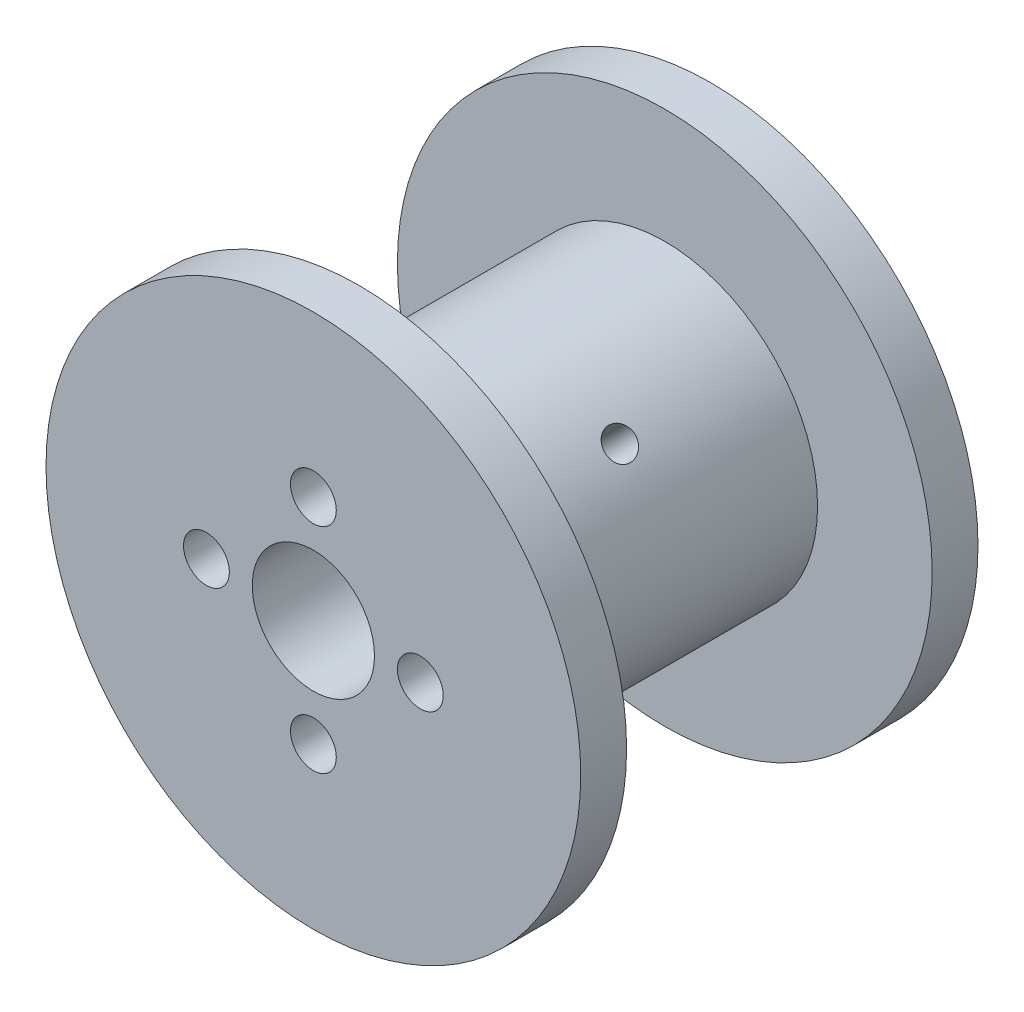
SolidWorks part; units mm, degrees
ref_plane "前视基准面" through (0, 0, 0) normal (0, 0, 1) x (1, 0, 0)
ref_plane "上视基准面" through (0, 0, 0) normal (0, 1, 0) x (1, 0, 0)
ref_plane "右视基准面" through (0, 0, 0) normal (1, 0, 0) x (0, 0, -1)
sketch "草图1" plane through (0, 0, 0) normal (0, 0, 1) x (1, 0, 0)
  circle A0 centre (0, 0) radius 17.5
  circle A2 centre (0, 7) radius 1.5
  circle A3 centre (7, 0) radius 1.5
  circle A4 centre (0, -7) radius 1.5
  circle A5 centre (-7, 0) radius 1.5
  circle A6 centre (0, 0) radius 4
  circle A7 centre (0, 0) radius 10
  point P15 (0, 0)
  dimension "D1" = 35
  dimension "D2" = 8
  dimension "D3" = 3
  dimension "D5" = 20
  dimension "D4" = 4
extrude "凸台-拉伸1" add sketch "草图1" along normal blind 23 contours A7 A2 A3 A4 A5 A6 | A0 A7 region at (-17.005, 0, 0) region at (-9.7172, 0, 0)
extrude "切除-拉伸1" cut sketch "草图1<4>" along normal blind 20 contours A0 A7 region at (-17.005, 0, 0)
sketch "草图1<4>" plane through (0, 0, 0) normal (0, 0, 1) x (1, 0, 0) same geometry as "草图1"
extrude "凸台-拉伸3" add sketch "草图1<5>" against normal blind 3 contours A7 A2 A3 A4 A5 A6 | A0 A7 region at (-17.005, 0, 0) region at (-9.7172, 0, 0)
sketch "草图1<5>" plane through (0, 0, 0) normal (0, 0, 1) x (1, 0, 0) same geometry as "草图1"
sketch "草图2" plane through (0, 0, 23) normal (0, 0, 1) x (1, 0, 0)
  line L0 (0, 0) -> (16.507, 16.507) construction
ref_plane "基准面4" through (7.0711, 7.0711, 0) normal (0.7071, 0.7071, 0) x (0.7071, -0.7071, 0)
sketch "草图3" plane through (7.0711, 7.0711, 0) normal (0.7071, 0.7071, 0) x (0.7071, -0.7071, 0)
  line L0 (-10, -10) -> (0, -10) construction
  line L1 (-10, 0) -> (-10, -20) construction
  circle A0 centre (0, -10) radius 1
  dimension "D2" = 2
  dimension "D1" = 10
extrude "切除-拉伸2" cut sketch "草图3" against normal blind 9
